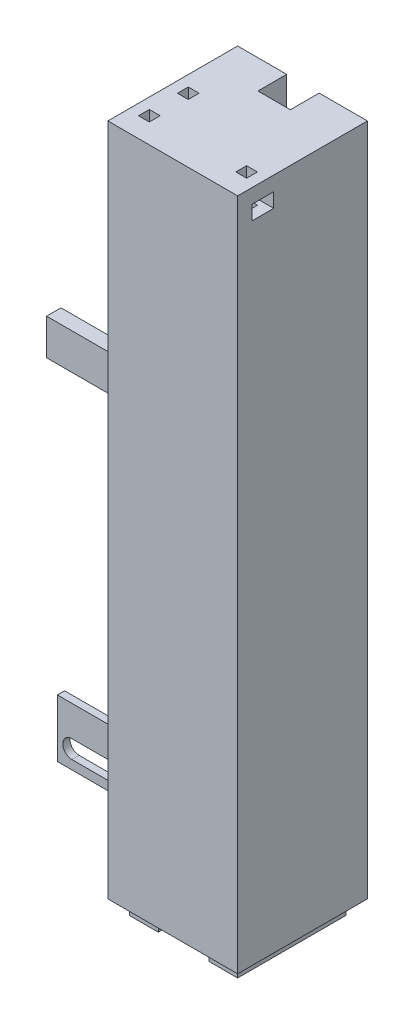
SolidWorks part; units mm, degrees
ref_plane "Front Plane" through (0, 0, 0) normal (0, 0, 1) x (1, 0, 0)
ref_plane "Top Plane" through (0, 0, 0) normal (0, 1, 0) x (1, 0, 0)
ref_plane "Right Plane" through (0, 0, 0) normal (1, 0, 0) x (0, 0, -1)
sketch "Sketch1" plane through (0, 0, 0) normal (0, 1, 0) x (1, 0, 0)
  line L1 (0, 0) -> (36, 0)
  line L2 (0, 0) -> (0, 36)
  line L3 (0, 36) -> (36, 36)
  line L4 (36, 0) -> (36, 36)
  dimension "D1" = 36
  dimension "D2" = 36
extrude "Boss-Extrude1" add sketch "Sketch1" along normal blind 186.9
sketch "Sketch2" plane through (0, 0, 0) normal (0, -1, 0) x (1, 0, 0)
  line L0 (0, 0) -> (36, 0) construction
  line L1 (3, -3) -> (7, -3)
  line L2 (3, -3) -> (3, -33)
  line L3 (3, -33) -> (7, -33)
  line L4 (7, -11) -> (7, -25)
  line L5 (36, -36) -> (0, -36) construction
  line L6 (0, -36) -> (0, 0) construction
  line L20 (36, 0) -> (36, -36) construction
  line L29 (7, -3) -> (11, -3)
  line L31 (7, -11) -> (11, -11)
  line L32 (11, -3) -> (11, -11)
  line L33 (7, -25) -> (11, -25)
  line L35 (7, -33) -> (11, -33)
  line L36 (11, -25) -> (11, -33)
  line L45 (29, -3) -> (33, -3)
  line L46 (29, -11) -> (29, -25)
  line L47 (29, -33) -> (33, -33)
  line L48 (33, -3) -> (33, -33)
  line L50 (29, -3) -> (25, -3)
  line L52 (29, -11) -> (25, -11)
  line L53 (25, -3) -> (25, -11)
  line L54 (29, -33) -> (25, -33)
  line L56 (29, -25) -> (25, -25)
  line L57 (25, -33) -> (25, -25)
  dimension "D1" = 3
  dimension "D2" = 3
  dimension "D3" = 3
  dimension "D4" = 4
  dimension "D5" = 4
  dimension "D6" = 8
  dimension "D7" = 8
  dimension "D8" = 4
  dimension "D9" = 3
  dimension "D10" = 3
  dimension "D11" = 3
  dimension "D12" = 4
  dimension "D13" = 4
  dimension "D14" = 4
extrude "Boss-Extrude2" add sketch "Sketch2" along normal blind 4
sketch "Sketch3" plane through (0, 0, 0) normal (0, -1, 0) x (1, 0, 0)
  line L0 (36, -36) -> (0, -36) construction
  line L2 (0, -36) -> (0, 0) construction
  circle A0 centre (18, -18) radius 2
  dimension "D1" = 4
  dimension "D2" = 18
  dimension "D3" = 18
extrude "Cut-Extrude1" cut sketch "Sketch3" against normal blind 5
sketch "Sketch4" plane through (0, 0, -36) normal (0, 0, 1) x (1, 0, 0)
  line L0 (0, 186.9) -> (36, 186.9) construction
  line L1 (13.62, 186.9) -> (22.62, 186.9)
  line L2 (13.62, 186.9) -> (13.62, 0)
  line L3 (13.62, 0) -> (22.62, 0)
  line L4 (22.62, 186.9) -> (22.62, 0)
  line L5 (0, 0) -> (36, 0) construction
  line L7 (36, 186.9) -> (36, 0) construction
  dimension "D1" = 13.38
  dimension "D2" = 9
extrude "Cut-Extrude2" cut sketch "Sketch4" along normal blind 8
sketch "Sketch5" plane through (36, 0, 0) normal (1, 0, 0) x (0, 0, -1)
  line L0 (0, 186.9) -> (36, 186.9) construction
  line L1 (4, 182.9) -> (10, 182.9)
  line L2 (4, 182.9) -> (4, 178.9)
  line L3 (4, 178.9) -> (10, 178.9)
  line L4 (10, 182.9) -> (10, 178.9)
  line L5 (0, 186.9) -> (0, 0) construction
  dimension "D1" = 6
  dimension "D2" = 4
  dimension "D3" = 4
  dimension "D4" = 4
extrude "Cut-Extrude3" cut sketch "Sketch5" against normal blind 9
sketch "Sketch6" plane through (0, 186.9, 0) normal (0, 1, 0) x (1, 0, 0)
  line L0 (36, 0) -> (36, 36) construction
  line L1 (30, 8.5) -> (33, 8.5)
  line L2 (30, 8.5) -> (30, 5.5)
  line L3 (30, 5.5) -> (33, 5.5)
  line L4 (33, 8.5) -> (33, 5.5)
  line L5 (0, 0) -> (36, 0) construction
  dimension "D1" = 3
  dimension "D2" = 3
  dimension "D3" = 3
  dimension "D4" = 5.5
extrude "Cut-Extrude4" cut sketch "Sketch6" against normal blind 10
sketch "Sketch7" plane through (0, 0, 0) normal (-1, 0, 0) x (0, 0, 1)
  line L0 (-36, 186.9) -> (-36, 0) construction
  line L1 (-28, 0) -> (-26, 0)
  line L2 (-28, 0) -> (-28, 16)
  line L3 (-28, 16) -> (-26, 16)
  line L4 (-26, 0) -> (-26, 16)
  dimension "D1" = 2
  dimension "D2" = 16
  dimension "D3" = 8
extrude "Boss-Extrude3" add sketch "Sketch7" along normal blind 40
sketch "Sketch8" plane through (0, 0, -26) normal (0, 0, 1) x (1, 0, 0)
  line L0 (-40, 0) -> (0, 0) construction
  line L1 (-40, 0) -> (-40, 16) construction
  line L3 (-36, 7.5) -> (-12, 7.5)
  line L5 (-36, 2.5) -> (-12, 2.5)
  arc A0 (-36, 7.5) -> (-36, 2.5) centre (-36, 5) ccw
  arc A1 (-12, 2.5) -> (-12, 7.5) centre (-12, 5) ccw
  dimension "D1" = 5
  dimension "D2" = 5
  dimension "D4" = 5
  dimension "D3" = 4
  dimension "D5" = 5
  dimension "D6" = 24
extrude "Cut-Extrude5" cut sketch "Sketch8" against normal up to next
sketch "Sketch9" plane through (0, 0, 0) normal (-1, 0, 0) x (0, 0, 1)
  line L0 (-26, 0) -> (0, 0) construction
  line L1 (-32, 103.5) -> (-28, 103.5)
  line L2 (-32, 103.5) -> (-32, 93.5)
  line L3 (-32, 93.5) -> (-28, 93.5)
  line L4 (-28, 103.5) -> (-28, 93.5)
  line L5 (-36, 186.9) -> (-36, 0) construction
  dimension "D1" = 103.5
  dimension "D2" = 10
  dimension "D3" = 4
  dimension "D4" = 4
extrude "Boss-Extrude4" add sketch "Sketch9" along normal blind 45
chamfer "Chamfer1" distance 20 angle 45 2 edges at (0, 93.5, -30) (0, 16, -27)
sketch "Sketch10" plane through (0, 0, -26) normal (0, 0, 1) x (1, 0, 0)
  line L0 (-17.1716, 93.5) -> (-2, 78.3284)
  line L1 (-2, 78.3284) -> (-2, 93.5)
  line L2 (-2, 93.5) -> (-17.1716, 93.5)
  line L3 (0, 186.9) -> (0, 0) construction
  line L4 (-20, 93.5) -> (0, 73.5) construction
  line L5 (-45, 93.5) -> (-20, 93.5) construction
  line L6 (-17.1716, 16) -> (-2, 31.1716)
  line L7 (-2, 31.1716) -> (-2, 16)
  line L8 (-2, 16) -> (-17.1716, 16)
  line L9 (0, 36) -> (-20, 16) construction
  line L10 (-40, 16) -> (-20, 16) construction
  dimension "D1" = 2
  dimension "D2" = 2
  dimension "D3" = 0
  dimension "D4" = 2
  dimension "D5" = 2
  dimension "D6" = 0
extrude "Cut-Extrude6" cut sketch "Sketch10" along direction (0, 0, -1) on the side against the normal blind 27
sketch "Sketch11" plane through (0, 0, 0) normal (-1, 0, 0) x (0, 0, 1)
  line L0 (-36, 186.9) -> (0, 186.9) construction
  line L1 (-4, 182.9) -> (-10, 182.9)
  line L2 (-4, 182.9) -> (-4, 178.9)
  line L3 (-4, 178.9) -> (-10, 178.9)
  line L4 (-10, 182.9) -> (-10, 178.9)
  line L5 (0, 186.9) -> (0, 0) construction
  line L7 (-14.8, 182.9) -> (-20.8, 182.9)
  line L8 (-14.8, 182.9) -> (-14.8, 178.9)
  line L9 (-14.8, 178.9) -> (-20.8, 178.9)
  line L10 (-20.8, 182.9) -> (-20.8, 178.9)
  line L11 (-16, 172.9) -> (-10, 172.9)
  line L12 (-16, 172.9) -> (-16, 166.9)
  line L13 (-16, 166.9) -> (-10, 166.9)
  line L14 (-10, 172.9) -> (-10, 166.9)
  dimension "D1" = 6
  dimension "D2" = 4
  dimension "D3" = 4
  dimension "D4" = 4
  dimension "D5" = 6
  dimension "D6" = 4.8
  dimension "D7" = 6
  dimension "D8" = 6
  dimension "D9" = 6
  dimension "D10" = 6
  dimension "D11" = 4
extrude "Cut-Extrude7" cut sketch "Sketch11" against normal blind 9
sketch "Sketch12" plane through (0, 186.9, 0) normal (0, 1, 0) x (1, 0, 0)
  line L0 (0, 0) -> (36, 0) construction
  line L1 (3, 8.5) -> (6, 8.5)
  line L2 (3, 8.5) -> (3, 5.5)
  line L3 (3, 5.5) -> (6, 5.5)
  line L4 (6, 8.5) -> (6, 5.5)
  line L5 (0, 36) -> (0, 0) construction
  line L7 (6, 16.3) -> (3, 16.3)
  line L8 (6, 16.3) -> (6, 19.3)
  line L9 (6, 19.3) -> (3, 19.3)
  line L10 (3, 16.3) -> (3, 19.3)
  dimension "D1" = 3
  dimension "D2" = 3
  dimension "D3" = 5.5
  dimension "D4" = 3
  dimension "D5" = 3
  dimension "D6" = 3
  dimension "D7" = 7.8
extrude "Cut-Extrude8" cut sketch "Sketch12" against normal blind 10
